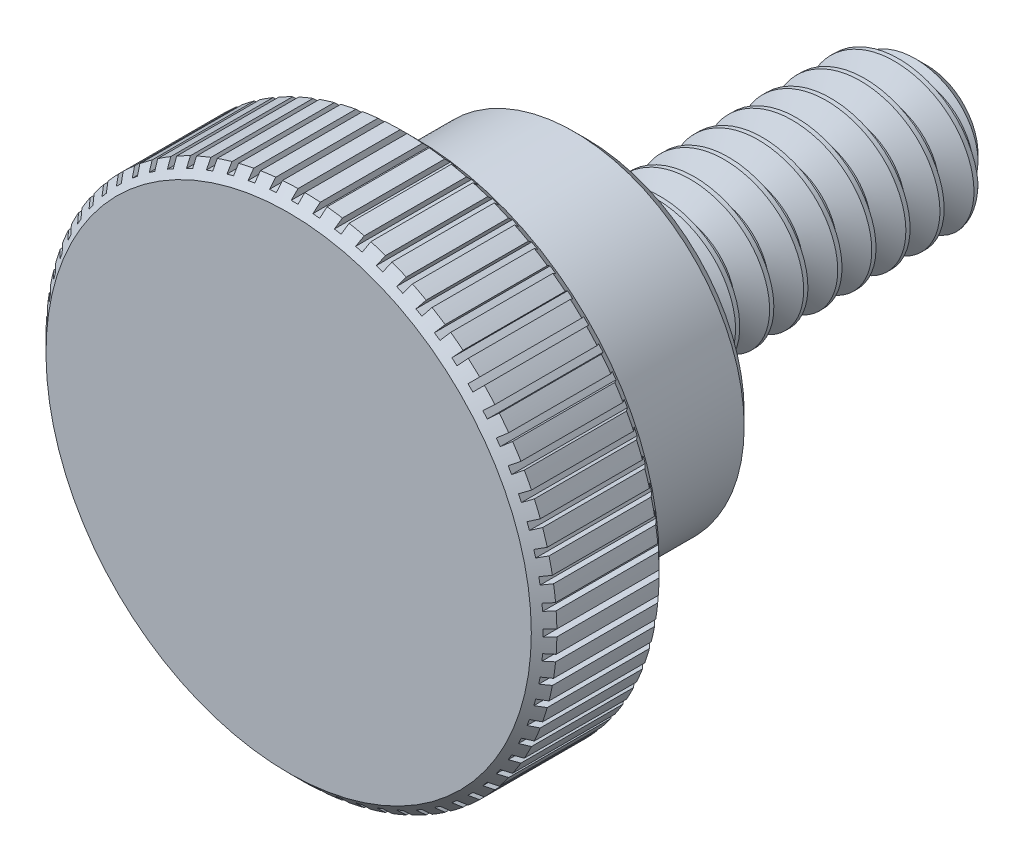
SolidWorks part; units mm, degrees
ref_plane "Front" through (0, 0, 0) normal (0, 0, 1) x (1, 0, 0)
ref_plane "Top" through (0, 0, 0) normal (0, 1, 0) x (1, 0, 0)
ref_plane "Right" through (0, 0, 0) normal (1, 0, 0) x (0, 0, -1)
sketch "Sketch20" plane through (0, 0, 0) normal (1, 0, 0) x (0, 0, -1)
  line L0 (0, 0) -> (6.35, 0) construction
  line L1 (6.35, 1.4224) -> (6.35, -1.4224) construction
  line L2 (-3.175, 4.7625) -> (-3.175, -4.7625) construction
  line L3 (-5.5562, 4.7625) -> (-5.5562, -4.7625) construction
  line L4 (0, 3.175) -> (0, -3.175) construction
  point P9 (3.4925, -1.4224)
  point P11 (-3.175, 0)
  point P14 (0, 0)
  dimension "D1" = 2.8448
  dimension "D2" = 6.35
  dimension "D3" = 2.8575
  dimension "Shoulder Diameter" = 6.35
  dimension "Shoulder Length" = 3.175
  dimension "Head Diameter" = 9.525
  dimension "Head Height" = 2.3813
sketch "Sketch1" plane through (0, 0, 0) normal (0, 0, 1) x (1, 0, 0)
  circle A0 centre (0, 0) radius 1.4224
  dimension "dia" = 2.8448
extrude "Extrude1" add sketch "Sketch1" against normal blind 6.35
chamfer "Chamfer2" distance 0.4763 angle 45 1 edges at (1.4224, 0, -6.35)
sketch "Sketch15" plane through (0, 0, -6.35) normal (0, 0, -1) x (-1, 0, 0)
  circle A0 centre (0, 0) radius 1.4224 construction
  circle A2 centre (0, 0) radius 1.4224
curve "Helix/Spiral1" pitch 0.635 height 6.985 turns 11 parameters "pitch"=0.635
sketch "Sketch14" plane through (0, 0, 0) normal (1, 0, 0) x (0, 0, -1)
  line L0 (6.35, 1.4224) -> (6.9056, 1.4224)
  line L1 (6.9056, 1.4224) -> (6.6675, 1.01)
  line L2 (6.6675, 1.01) -> (6.5881, 1.01)
  line L3 (6.5881, 1.01) -> (6.35, 1.4224)
  line L4 (6.4691, 1.2162) -> (6.7866, 1.2162) construction
  line L5 (6.35, -1.4224) -> (6.35, 1.4224) construction
  dimension "D1" = 0.0794
  dimension "D2" = 0.3175
  dimension "D3" = 60
sweep "Cut-Sweep1" cut profiles "Sketch14" path "Helix/Spiral1" align with end faces yes
sketch "Sketch27" plane through (0, 0, 0) normal (0, 0, 1) x (1, 0, 0)
  circle A0 centre (0, 0) radius 3.175
extrude "Boss-Extrude4" add sketch "Sketch27" along normal up to vertex (3.175 mm away) up to point (0, 0, 3.175)
sketch "Sketch21" plane through (0, 0, 3.175) normal (0, 0, 1) x (1, 0, 0)
  line L0 (-4.7625, 0) -> (4.7625, 0) construction
  circle A0 centre (0, 0) radius 4.7625
extrude "Boss-Extrude1" add sketch "Sketch21" along normal up to vertex (2.3813 mm away) up to point (0, -4.7625, 5.5562)
chamfer "Chamfer3" distance 0.2381 angle 45 3 edges at (4.7625, 0, 3.175) (4.7625, 0, 5.5562) (3.175, 0, 0)
fillet "Fillet1" radius 0.2381 1 edges at (3.175, 0, 3.175)
ref_plane "Plane1" through (0, 4.7625, 0) normal (0, 1, 0) x (-1, 0, 0)
sketch "Sketch22" plane through (0, 4.7625, 0) normal (0, 1, 0) x (-1, 0, 0)
  line L0 (0, 5.5562) -> (0, 3.175) construction
  line L1 (-0.0635, 5.5562) -> (0.0635, 5.5562)
  line L3 (-0.0635, 5.5562) -> (-0.0635, 3.175)
  line L4 (-0.0635, 3.175) -> (0.0635, 3.175)
  line L7 (0.0635, 5.5562) -> (0.0635, 3.175)
  dimension "D1" = 0.127
extrude "Cut-Extrude1" cut sketch "Sketch22" against normal offset from surface (0.1274 mm away) 0.127
pattern_circular "CirPattern1" count 72 over 360 about axis through (0, 0, 0) along (0, 0, 1) of "Cut-Extrude1"
equation "\"D3@Helix/Spiral1\" = \"Lg@Extrude1\"+\"pitch@Helix/Spiral1\""
equation "\"D1@Sketch14\" = \"pitch@Helix/Spiral1\" * .125"
equation "\"D2@Sketch14\" = \"pitch@Helix/Spiral1\" * .5"
equation "\"D1@Chamfer2\" = \"pitch@Helix/Spiral1\" * .75"
equation "\"D1@Sketch20\" = \"dia@Sketch1\""
equation "\"D2@Sketch20\" = \"Lg@Extrude1\""
equation "\"D1@Chamfer3\" =\"Head Height@Sketch20\"/10"
equation "\"D3@Sketch20\" = \"pitch@Helix/Spiral1\"*4.50"
equation "\"D1@Fillet1\" = \"D1@Chamfer3\""
